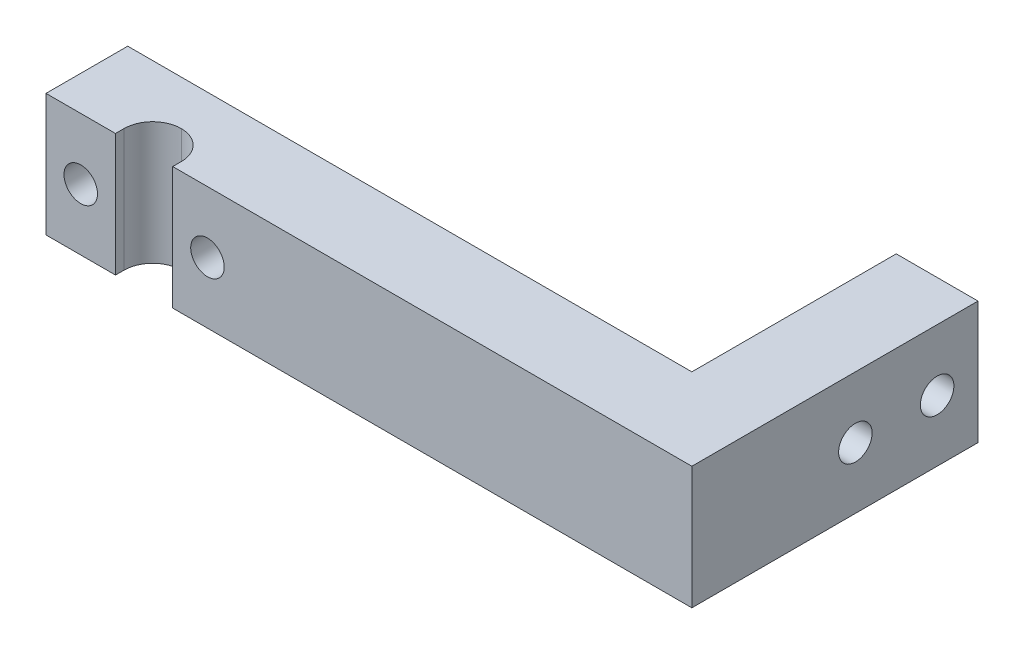
SolidWorks part; units mm, degrees
ref_plane "Спереди" through (0, 0, 0) normal (0, 0, 1) x (1, 0, 0)
ref_plane "Сверху" through (0, 0, 0) normal (0, 1, 0) x (1, 0, 0)
ref_plane "Справа" through (0, 0, 0) normal (1, 0, 0) x (0, 0, -1)
sketch "Sketch1" plane through (0, 0, 0) normal (0, 1, 0) x (1, 0, 0)
  line L0 (-22.986, 8.6014) -> (-22.986, -11.3986)
  line L1 (-22.986, -11.3986) -> (-5.986, -11.3986)
  line L2 (-5.986, -11.3986) -> (-5.986, -2.3077)
  line L3 (-5.986, -2.3077) -> (8.014, -2.3077)
  line L4 (8.014, -2.3077) -> (8.014, -11.3986)
  line L5 (8.014, -11.3986) -> (25.014, -11.3986)
  line L6 (25.014, -11.3986) -> (25.014, 8.6014)
  line L7 (25.014, 8.6014) -> (6.014, 8.6014)
  line L8 (6.014, 8.6014) -> (6.014, 58.6014)
  line L9 (6.014, 58.6014) -> (-3.986, 58.6014)
  line L10 (-3.986, 58.6014) -> (-3.986, 8.6014)
  line L11 (-3.986, 8.6014) -> (-22.986, 8.6014)
  dimension "D1" = 20
  dimension "D2" = 48
  dimension "D3" = 50
  dimension "D4" = 10
  dimension "D5" = 14
extrude "Boss-Extrude1" add sketch "Sketch1" along normal blind 30
sketch "Sketch3" plane through (0, 0, 11.3986) normal (0, 0, 1) x (1, 0, 0)
  line L0 (-22.986, 15) -> (-5.986, 15) construction
  line L1 (-22.986, 30) -> (-22.986, 0) construction
  line L2 (-5.986, 30) -> (-5.986, 0) construction
  line L4 (8.014, 15) -> (25.014, 15) construction
  line L5 (8.014, 30) -> (8.014, 0) construction
  line L6 (25.014, 30) -> (25.014, 0) construction
  circle A0 centre (-14.486, 15) radius 4.1
  circle A1 centre (16.514, 15) radius 4.1
  dimension "D1" = 8.2
extrude "Cut-Extrude1" cut sketch "Sketch3" against normal through all
sketch "Sketch4" plane through (6.014, 0, 0) normal (1, 0, 0) x (0, 0, -1)
  line L0 (58.6014, 15) -> (8.6014, 15) construction
  line L1 (58.6014, 30) -> (58.6014, 0) construction
  line L2 (8.6014, 30) -> (8.6014, 0) construction
  circle A0 centre (28.6014, 15) radius 4.1
  circle A1 centre (48.6014, 15) radius 4.1
  dimension "D1" = 8.2
  dimension "D2" = 20
  dimension "D3" = 20
extrude "Cut-Extrude2" cut sketch "Sketch4" against normal through all
fillet "Fillet1" radius 7 2 edges at (-5.986, 15, 2.3077) (8.014, 15, 2.3077)
sketch "Sketch6" plane through (0, 0, 0) normal (0, -1, 0) x (1, 0, 0)
  line L0 (25.014, 11.3986) -> (135.014, 11.3986)
  line L1 (135.014, 11.3986) -> (135.014, -58.6014)
  line L2 (135.014, -58.6014) -> (115.014, -58.6014)
  line L3 (115.014, -58.6014) -> (115.014, -8.6014)
  line L4 (115.014, -8.6014) -> (25.014, -8.6014)
  line L5 (25.014, -8.6014) -> (25.014, 11.3986)
  line L7 (6.014, -8.6014) -> (6.014, -58.6014) construction
  dimension "D1" = 90
  dimension "D2" = 110
extrude "Boss-Extrude2" add sketch "Sketch6" against normal up to surface (30 mm away) up to face at (1.014, 30, -6.7685)
sketch "Sketch7" plane through (-3.986, 0, 0) normal (-1, 0, 0) x (0, 0, 1)
  circle A0 centre (-48.6014, 15) radius 4.1
  circle A1 centre (-28.6014, 15) radius 4.1
  circle A2 centre (-28.6014, 15) radius 4.1 construction
  circle A3 centre (-48.6014, 15) radius 4.1 construction
extrude "Cut-Extrude3" cut sketch "Sketch7" against normal through all
sketch "Sketch8" plane through (0, 30, 0) normal (0, 1, 0) x (1, 0, 0)
  line L0 (6.014, 8.6014) -> (-3.986, 8.6014)
  line L1 (-3.986, 8.6014) -> (-3.986, 58.6014)
  line L2 (-3.986, 58.6014) -> (6.014, 58.6014)
  line L3 (6.014, 58.6014) -> (6.014, 8.6014)
extrude "Cut-Extrude4" cut sketch "Sketch8" against normal through all
